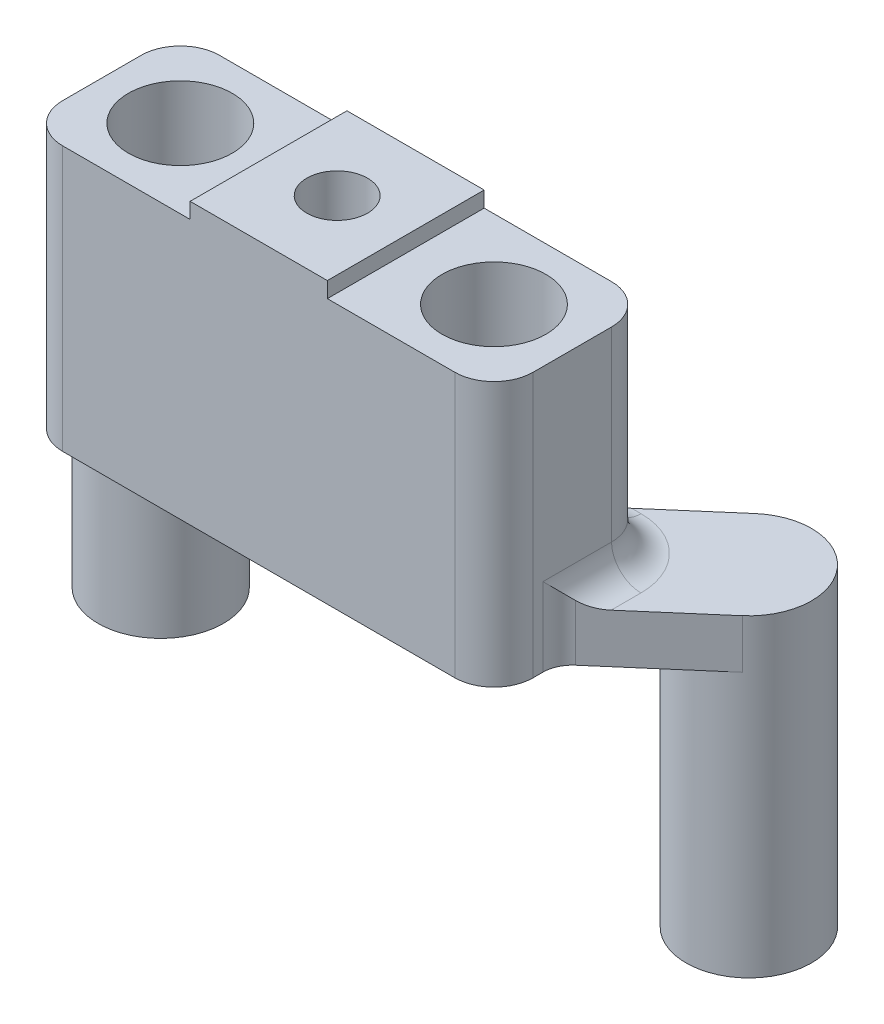
SolidWorks part; units mm, degrees
ref_plane "Front Plane" through (0, 0, 0) normal (0, 0, 1) x (1, 0, 0)
ref_plane "Top Plane" through (0, 0, 0) normal (0, 1, 0) x (1, 0, 0)
ref_plane "Right Plane" through (0, 0, 0) normal (1, 0, 0) x (0, 0, -1)
ref_axis "X-Axis" through (-88.4377, 0, 0) along (1, 0, 0)
ref_axis "Y-Axis" through (0, 0, -69.2525) along (0, 0, 1)
ref_axis "Z-Axis" through (0, -52.5493, 0) along (0, 1, 0)
sketch "Sketch25" plane through (0, 0, 0) normal (0, 1, 0) x (-1, 0, 0)
  line L8 (3.5, -4) -> (-3.5, -4)
  line L9 (3.5, -4) -> (3.5, 4)
  line L10 (3.5, 4) -> (-3.5, 4)
  line L11 (-3.5, -4) -> (-3.5, 4)
  line L12 (3.5, -4) -> (-3.5, 4) construction
  line L13 (3.5, 4) -> (-3.5, -4) construction
  point P8 (0, 0)
  dimension "D3" = 7
  dimension "D1" = 8
extrude "Boss-Extrude5" add sketch "Sketch25" along normal blind 12.8
sketch "Sketch26" plane through (0, 0, 0) normal (0, 1, 0) x (-1, 0, 0)
  line L0 (0, 4) -> (0, -4) construction
  line L1 (-12, -4) -> (12, -4)
  line L2 (-12, -4) -> (-12, 4)
  line L3 (-12, 4) -> (12, 4)
  line L4 (12, -4) -> (12, 4)
  line L5 (-12, 0) -> (12, 0) construction
  line L6 (-8, 0) -> (0, -4) construction
  line L7 (0, -4) -> (8, 0) construction
  line L10 (-3.5, -4) -> (3.5, -4) construction
  line L11 (3.5, 4) -> (-3.5, 4) construction
  circle A0 centre (-8, 0) radius 2.65
  circle A1 centre (8, 0) radius 2.65
  dimension "D2" = 5.3
  dimension "D1" = 24
  dimension "D3" = 16
extrude "Boss-Extrude6" add sketch "Sketch26" along normal blind 12 and the other way blind 1.5
sketch "Sketch27" plane through (0, 12.8, 0) normal (0, 1, 0) x (1, 0, 0)
  circle A0 centre (0, 0) radius 1.55
  dimension "D1" = 3.1
extrude "Cut-Extrude1" cut sketch "Sketch27" against normal blind 6.5
fillet "Fillet1" radius 2 4 edges at (-12, 5.25, 4) (12, 5.25, 4) (-12, 5.25, -4) (12, 5.25, -4)
sketch "Sketch29" plane through (0, -1.5, 0) normal (0, -1, 0) x (1, 0, 0)
  line L0 (0, 0) -> (0, 32) construction
  line L1 (0, 32) -> (-15, 32) construction
  line L2 (-15, 32) -> (-15, -6) construction
  line L3 (-17.0908, -3.5775) -> (-12, 0.8163)
  line L4 (-12.9092, -8.4225) -> (-7.7851, -4)
  line L8 (17.0908, -3.5775) -> (12, 0.8163)
  line L11 (12.9092, -8.4225) -> (7.7851, -4)
  line L12 (-12, -2) -> (-12, 2) construction
  line L13 (-3.5, -4) -> (-10, -4) construction
  line L14 (-12, -2) -> (-12, 2) construction
  line L16 (10, -4) -> (-10, -4) construction
  line L17 (-12, 0.8163) -> (-10.746, -2.4227)
  line L18 (-10.746, -2.4227) -> (-7.7851, -4)
  line L19 (12, 0.8163) -> (10.7912, -2.6069)
  line L20 (10.7912, -2.6069) -> (7.7851, -4)
  line L21 (12, 2) -> (12, -2) construction
  arc A1 (-17.0908, -3.5775) -> (-12.9092, -8.4225) centre (-15, -6) ccw
  arc A3 (17.0908, -3.5775) -> (12.9092, -8.4225) centre (15, -6) cw
  point P3 (-12, 2)
  point P9 (0, 0)
  point P14 (12, 0.8163)
  point P28 (10.7912, -2.6069)
  point P29 (-10.746, -2.4227)
  dimension "D5" = 6.4
  dimension "D1" = 32
  dimension "D2" = 38
  dimension "D3" = 15
extrude "Boss-Extrude8" add sketch "Sketch29" against normal blind 2.5
fillet "Fillet2" radius 1.5 10 edges at (12, 1, -0.5918) (11.4142, 1, -3.4142) (-8.8926, 1, -4) (-11.4142, 1, -3.4142) (-12, -0.25, 0.8163) (12, -0.25, 0.8163) (-7.7851, -0.25, -4) (7.7851, -0.25, -4) (8.8926, 1, -4) (-12, 1, -0.5918)
sketch "Sketch30" plane through (0, -1.5, 0) normal (0, -1, 0) x (1, 0, 0)
  circle A0 centre (-15, -6) radius 3.2
  circle A1 centre (15, -6) radius 3.2
  point P5 (15, -6)
  dimension "D1" = 30
  dimension "D2" = 6.4
extrude "Boss-Extrude9" add sketch "Sketch30" along normal blind 13.5
sketch "Sketch31" plane through (0, -15, 0) normal (0, -1, 0) x (1, 0, 0)
  circle A0 centre (-15, -6) radius 2.25
  circle A1 centre (15, -6) radius 2.25
  dimension "D1" = 4.5
extrude "Cut-Extrude2" cut sketch "Sketch31" against normal blind 4
